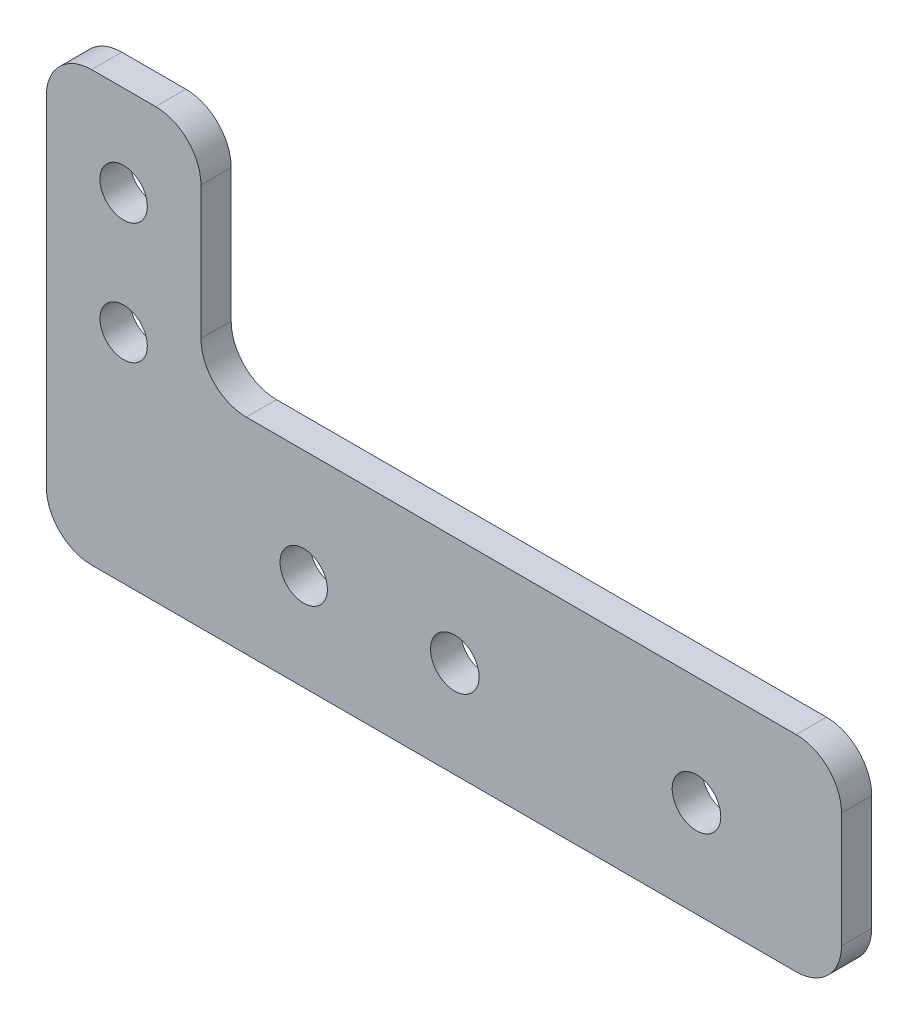
SolidWorks part; units mm, degrees
material "6061-T6 (SS)"
ref_plane "Front Plane" through (0, 0, 0) normal (0, 0, 1) x (1, 0, 0)
ref_plane "Top Plane" through (0, 0, 0) normal (0, 1, 0) x (1, 0, 0)
ref_plane "Right Plane" through (0, 0, 0) normal (1, 0, 0) x (0, 0, -1)
sketch "Sketch1" plane through (0, 0, 0) normal (0, 0, 1) x (1, 0, 0)
  line L0 (-21.59, 23.8125) -> (-37.846, 23.8125) construction
  line L1 (-45.72, -23.8125) -> (45.72, -23.8125)
  line L2 (-45.72, -23.8125) -> (-45.72, 23.8125)
  line L3 (-45.72, 23.8125) -> (45.72, 23.8125)
  line L4 (45.72, -23.8125) -> (45.72, 23.8125)
  line L5 (-45.72, -23.8125) -> (45.72, 23.8125) construction
  line L6 (-45.72, 23.8125) -> (45.72, -23.8125) construction
  line L7 (45.72, 23.8125) -> (-21.59, 23.8125)
  line L8 (45.72, 23.8125) -> (45.72, 0.3175)
  line L9 (45.72, 0.3175) -> (-21.59, 0.3175)
  line L10 (-21.59, 23.8125) -> (-21.59, 0.3175)
  line L11 (-45.72, -23.8125) -> (-37.846, -23.8125)
  line L12 (-45.72, -23.8125) -> (-45.72, 23.8125)
  line L13 (-45.72, 23.8125) -> (-37.846, 23.8125)
  line L14 (-37.846, -23.8125) -> (-37.846, 23.8125)
  line L15 (-37.846, -23.8125) -> (45.72, -23.8125)
  line L16 (-37.846, -23.8125) -> (-37.846, -21.2725)
  line L17 (-37.846, -21.2725) -> (45.72, -21.2725)
  line L18 (45.72, -23.8125) -> (45.72, -21.2725)
  line L19 (-21.59, 23.8125) -> (-37.846, 23.8125) construction
  line L20 (-29.718, 23.8125) -> (-29.718, -21.2725) construction
  circle A0 centre (-29.718, -11.1125) radius 2.4892
  circle A1 centre (-29.718, 1.5875) radius 2.4892
  circle A2 centre (-29.718, 14.2875) radius 2.4892
  circle A4 centre (-10.795, -11.1125) radius 2.4892
  circle A5 centre (5.08, -11.1125) radius 2.5527
  circle A7 centre (30.48, -11.1125) radius 2.5527
  point P0 (0, 0)
  point P31 (0, 0)
  point P32 (0, 0)
  point P33 (0, 0)
  dimension "D7" = 15.24
  dimension "D18" = 5.1054
  dimension "D19" = 4.9784
  dimension "D13" = 25.4
  dimension "D1" = 91.44
  dimension "D2" = 9.525
  dimension "D3" = 24.13
  dimension "D4" = 24.13
  dimension "D5" = 7.874
  dimension "D6" = 47.625
  dimension "D9" = 12.7
  dimension "D10" = 12.7
  dimension "D11" = 12.7
  dimension "D15" = 15.875
  dimension "D16" = 2.54
extrude "Boss-Extrude1" add sketch "Sketch1" along normal blind 3.175 contours L14 L17 L4 L9 L10 L3 A5 A4 A2 A1 A0 | A0 region at (-1.4655, -6.6351, 0) region at (-29.718, -11.1125, 0)
fillet "Fillet1" radius 4.7625 6 edges at (-37.846, 23.8125, 1.5875) (-21.59, 23.8125, 1.5875) (-21.59, 0.3175, 1.5875) (45.72, 0.3175, 1.5875) (45.72, -21.2725, 1.5875) (-37.846, -21.2725, 1.5875)
